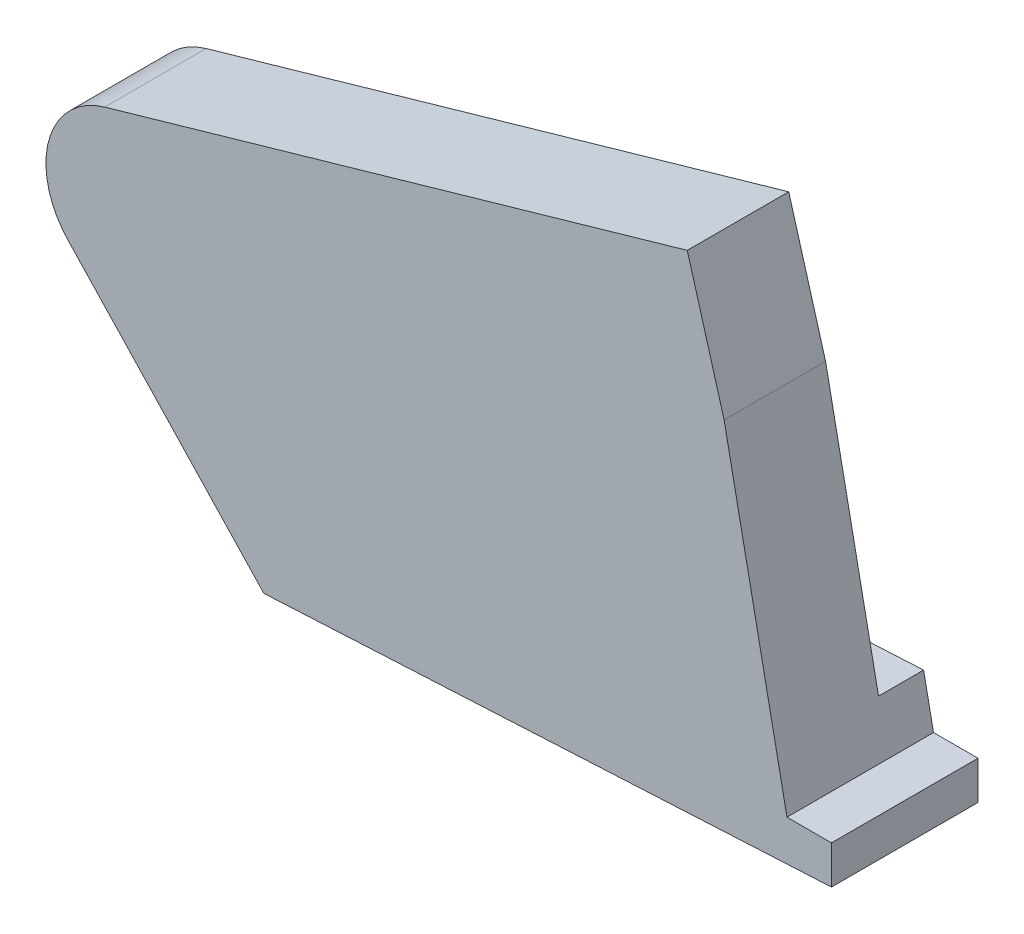
SolidWorks part; units mm, degrees
ref_plane "Front Plane" through (0, 0, 0) normal (0, 0, 1) x (1, 0, 0)
ref_plane "Top Plane" through (0, 0, 0) normal (0, 1, 0) x (1, 0, 0)
ref_plane "Right Plane" through (0, 0, 0) normal (1, 0, 0) x (0, 0, -1)
sketch "Sketch1" plane through (0, 0, 0) normal (0, 0, 1) x (1, 0, 0)
  line L0 (73.8608, -499.4378) -> (173.9171, -470.7181)
  line L1 (173.9171, -470.7181) -> (179.1078, -488.8016)
  line L2 (179.1078, -488.8016) -> (187.9598, -532.8268)
  line L3 (187.9598, -532.8268) -> (194.2233, -532.8268)
  line L4 (194.2233, -532.8268) -> (194.2233, -538.2227)
  line L5 (194.2233, -538.2227) -> (114.2863, -542.3701)
  line L6 (114.2863, -542.3701) -> (73.8608, -499.4378)
  point P2 (70.7182, -496.1003)
  point P9 (68.851, -500.8758)
extrude "Boss-Extrude1" add sketch "Sketch1" along normal blind 14.2875
sketch "Sketch2" plane through (0, 0, 0) normal (0, 0, -1) x (-1, 0, 0)
  line L0 (-194.2233, -532.8268) -> (-187.9598, -532.8268) construction
  line L1 (-194.2233, -538.2227) -> (-194.2233, -532.8268) construction
  line L2 (-114.2863, -542.3701) -> (-194.2233, -538.2227) construction
  line L3 (-194.2233, -532.8268) -> (-187.9598, -532.8268)
  line L4 (-194.2233, -538.2227) -> (-194.2233, -532.8268)
  line L5 (-114.2863, -542.3701) -> (-194.2233, -538.2227)
  line L6 (-187.9598, -532.8268) -> (-186.5676, -525.9029)
  line L7 (-187.9598, -532.8268) -> (-179.1078, -488.8016) construction
  line L8 (-186.5676, -525.9029) -> (-120.5846, -529.3263)
  line L9 (-120.5846, -529.3263) -> (-114.2863, -542.3701)
  line L12 (-159.3682, -443.3253) -> (-74.971, -618.1138) construction
  point P3 (-120.059, -530.4148)
  dimension "D1" = 12.7
extrude "Boss-Extrude2" add sketch "Sketch2" along normal blind 6.35
fillet "Fillet4" radius 11.43 1 edges at (73.8608, -499.4378, 7.1437)
